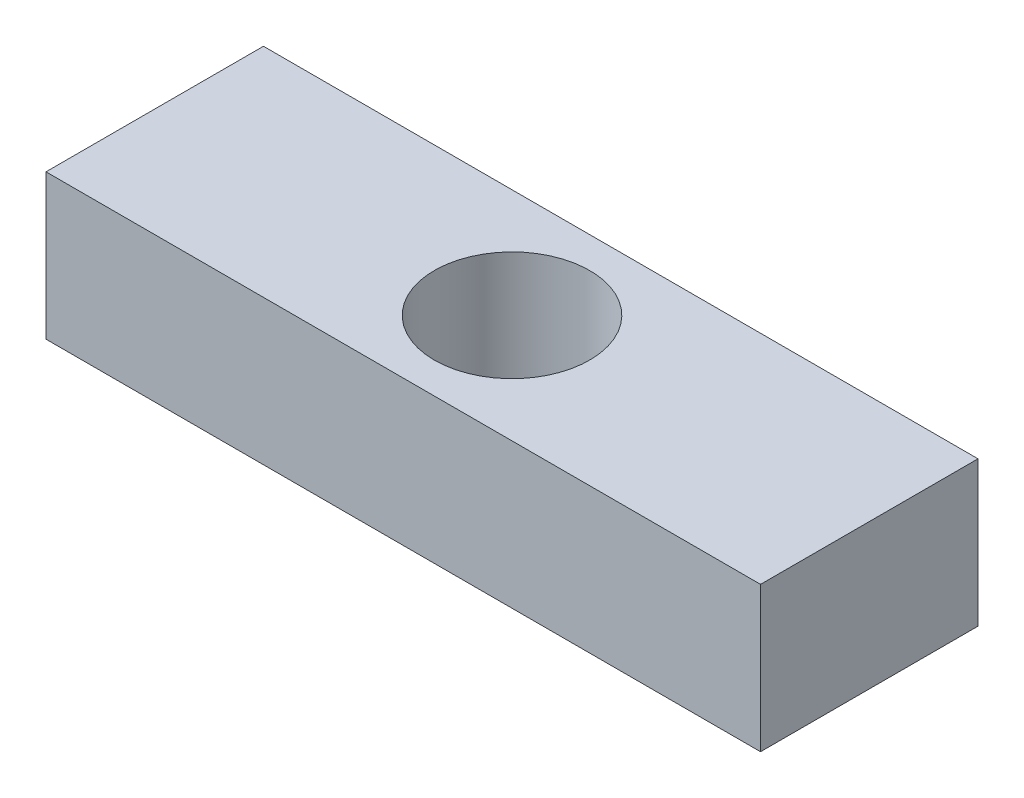
SolidWorks part; units mm, degrees
ref_plane "Front Plane" through (0, 0, 0) normal (0, 0, 1) x (1, 0, 0)
ref_plane "Top Plane" through (0, 0, 0) normal (0, 1, 0) x (1, 0, 0)
ref_plane "Right Plane" through (0, 0, 0) normal (1, 0, 0) x (0, 0, -1)
sketch "Sketch1" plane through (0, 0, 0) normal (0, 1, 0) x (1, 0, 0)
  line L1 (-69, -21) -> (69, -21)
  line L2 (-69, -21) -> (-69, 21)
  line L3 (-69, 21) -> (69, 21)
  line L4 (69, -21) -> (69, 21)
  line L5 (-69, -21) -> (69, 21) construction
  line L6 (-69, 21) -> (69, -21) construction
  circle A0 centre (0, 0) radius 15
  point P0 (0, 0)
extrude "Boss-Extrude1" add sketch "Sketch1" along normal blind 28
